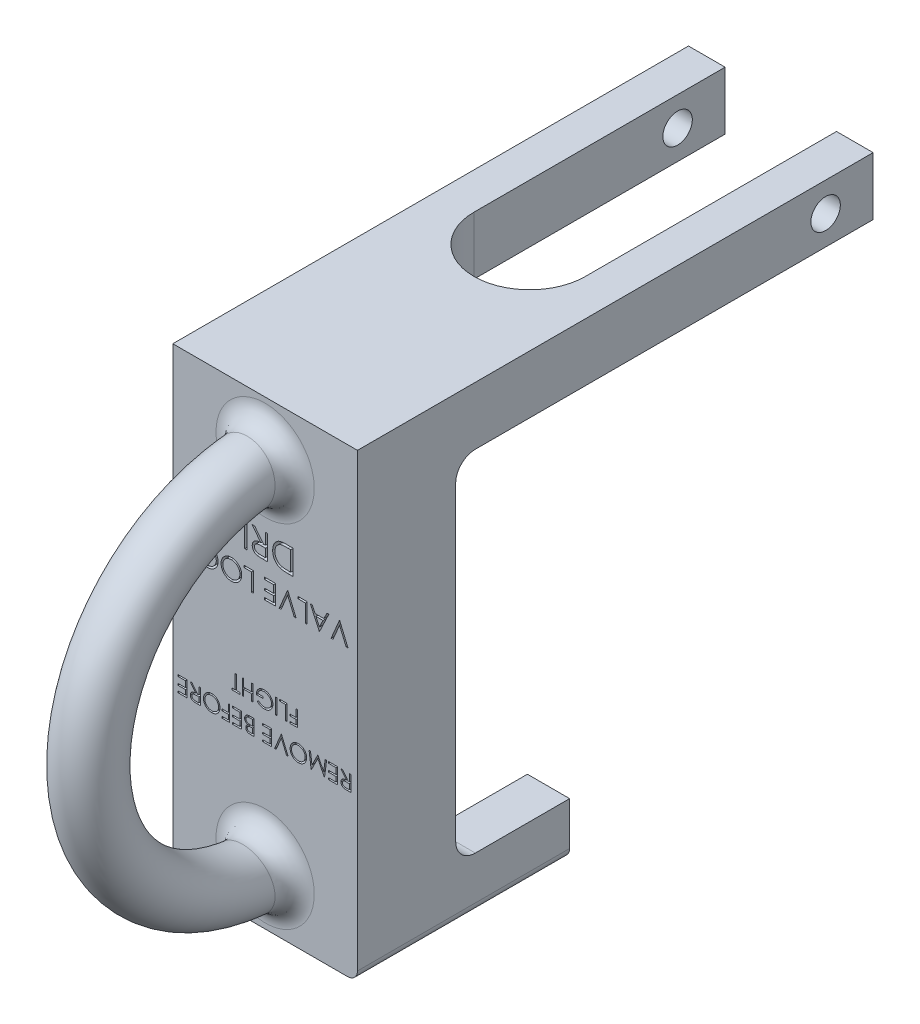
SolidWorks part; units mm, degrees
material "ABS PC"
ref_plane "Front Plane" through (0, 0, 0) normal (0, 0, 1) x (1, 0, 0)
ref_plane "Top Plane" through (0, 0, 0) normal (0, 1, 0) x (1, 0, 0)
ref_plane "Right Plane" through (0, 0, 0) normal (1, 0, 0) x (0, 0, -1)
sketch "Sketch1" plane through (0, 0, 0) normal (0, 0, 1) x (1, 0, 0)
  line L0 (0, 2.5) -> (0, -5) construction
  line L1 (-11.938, -5) -> (11.938, -5)
  line L2 (-11.938, -5) -> (-11.938, 2.5)
  line L3 (-11.938, 2.5) -> (11.938, 2.5)
  line L4 (11.938, -5) -> (11.938, 2.5)
  circle A0 centre (0, 0) radius 1.5
  dimension "D1" = 3
  dimension "D2" = 23.876
  dimension "D3" = 5
  dimension "D4" = 2.5
extrude "Boss-Extrude2" add sketch "Sketch1" along normal blind 21.59 contours L0 L3 L2 L1 A0 | L0 A0 | A0 L0 | L3 L0 A0 L1 L4 region at (6.1881, -1.3014, 0) region at (-6.1881, -1.3014, 0) region at (0.6366, 0, 0) region at (-0.6366, 0, 0)
ref_plane "Plane1" through (0, -1.25, 0) normal (0, 1, 0) x (1, 0, 0)
sketch "Sketch15" plane through (0, 2.5, 0) normal (0, 1, 0) x (1, 0, 0)
  line L0 (-11.938, 0) -> (11.938, 0) construction
  line L1 (-11.938, 0) -> (11.938, 0)
  line L3 (-11.938, 0) -> (11.938, 0)
  line L7 (-7.2, 12.61) -> (7.2, 12.61) construction
  line L10 (-11.938, 0) -> (-11.938, 45.085)
  line L11 (-11.938, 45.085) -> (-7.2, 45.085)
  line L12 (-7.2, 12.61) -> (-7.2, 45.085)
  line L14 (7.2, 12.61) -> (7.2, 45.085)
  line L15 (7.2, 45.085) -> (11.938, 45.085)
  line L16 (11.938, 0) -> (11.938, 45.085)
  arc A0 (-7.2, 12.61) -> (7.2, 12.61) centre (0, 12.61) ccw
  line M5 (11.938, 0) -> (-11.938, 0)
  dimension "D2" = 7.2
  dimension "D1" = 45.085
  dimension "D3" = 12.61
extrude "Boss-Extrude3" add sketch "Sketch15" against normal up to surface (7.5 mm away) contours A0 M5 region at (-11.4278, 2.5, -22.5425) up to face at (0, -5, 10.795)
sketch "Sketch19" plane through (0, -5, 0) normal (0, 1, 0) x (1, 0, 0)
  line L0 (-6.477, -13.462) -> (6.477, -13.462)
  line L1 (-11.938, -21.59) -> (11.938, -21.59) construction
  line L2 (-6.477, -13.462) -> (-6.477, -8.89)
  line L3 (-6.477, -8.89) -> (-11.938, -8.89)
  line L4 (-11.938, -21.59) -> (-11.938, 45.085) construction
  line L5 (-11.938, -8.89) -> (-11.938, -21.59)
  line L6 (-11.938, -21.59) -> (11.938, -21.59)
  line L7 (11.938, -21.59) -> (11.938, -8.89)
  line L8 (11.938, -21.59) -> (11.938, 45.085) construction
  line L9 (11.938, -8.89) -> (6.477, -8.89)
  line L10 (6.477, -8.89) -> (6.477, -13.462)
  point P10 (0, -13.462)
  point P17 (0, -21.59)
  dimension "D1" = 8.128
  dimension "D2" = 12.954
  dimension "D3" = 12.7
extrude "Boss-Extrude4" add sketch "Sketch19" against normal blind 48.26
sketch "Sketch20" plane through (11.938, 0, 0) normal (1, 0, 0) x (0, 0, -1)
  line L0 (45.085, -5) -> (45.085, 2.5) construction
  circle A0 centre (38.9382, -1.25) radius 1.905
  point P5 (45.085, -1.25)
  dimension "D2" = 3.81
  dimension "D1" = 6.1468
extrude "Cut-Extrude1" cut sketch "Sketch20" against normal through all
fillet "Fillet1" radius 2.54 2 edges at (6.477, -29.13, 13.462) (-6.477, -29.13, 13.462)
fillet "Fillet2" radius 2.54 2 edges at (-9.2075, -5, 8.89) (9.2075, -5, 8.89)
fillet "Fillet3" radius 2.54 5 edges at (6.477, -5, 8.636) (5.7331, -5, 12.7181) (0, -5, 13.462) (-5.7331, -5, 12.7181) (-6.477, -5, 8.636)
sketch "Sketch21" plane through (0, 0, 8.89) normal (0, 0, -1) x (-1, 0, 0)
  line L0 (11.938, -53.26) -> (11.938, -7.54) construction
  line L1 (6.477, -53.26) -> (11.938, -53.26)
  line L2 (6.477, -53.26) -> (6.477, -50.212)
  line L3 (6.477, -50.212) -> (11.938, -50.212)
  line L4 (11.938, -53.26) -> (11.938, -50.212)
  line L5 (-11.938, -53.26) -> (-11.938, -7.54) construction
  line L6 (-6.477, -53.26) -> (-11.938, -53.26)
  line L7 (-6.477, -53.26) -> (-6.477, -50.212)
  line L8 (-6.477, -50.212) -> (-11.938, -50.212)
  line L9 (-11.938, -53.26) -> (-11.938, -50.212)
  dimension "D1" = 3.048
extrude "Boss-Extrude5" add sketch "Sketch21" along normal blind 14.732
fillet "Fillet4" radius 2.54 2 edges at (-9.2075, -50.212, 8.89) (9.2075, -50.212, 8.89)
sketch "Sketch29" plane through (0, 0, 21.59) normal (0, 0, 1) x (1, 0, 0)
  line L0 (11.938, -34.21) -> (-11.938, -34.21) construction
  line L1 (11.938, -53.26) -> (11.938, 2.5) construction
  line L2 (-11.938, -53.26) -> (-11.938, 2.5) construction
  line L3 (11.938, -17.7) -> (-11.938, -17.7) construction
  line L4 (11.938, -30.4) -> (-11.938, -30.4) construction
  line L5 (11.938, -12.62) -> (-11.938, -12.62) construction
  line L6 (-11.938, -53.26) -> (11.938, -53.26) construction
  text T0 "REMOVE BEFORE" font "Century Gothic" height 2.032
  text T1 "FLIGHT" font "Century Gothic" height 2.032
  text T2 "VALVE LOCK" font "Century Gothic" height 2.54
  text T3 "DRL"
  dimension "D1" = 3.81
  dimension "D2" = 19.05
  dimension "D3" = 12.7
  dimension "D4" = 5.08
extrude "Cut-Extrude2" cut sketch "Sketch29" against normal blind 2.54
sketch "Sketch30" plane through (0, -53.26, 0) normal (0, -1, 0) x (1, 0, 0)
  line L14 (-6.477, -5.842) -> (-6.477, 10.922)
  line L15 (-3.937, 13.462) -> (3.937, 13.462)
  line L24 (6.477, 10.922) -> (6.477, -5.842)
  line L25 (6.477, -5.842) -> (11.938, -5.842)
  line L26 (11.938, -5.842) -> (11.938, 21.59)
  line L27 (11.938, 21.59) -> (-11.938, 21.59)
  line L28 (-11.938, 21.59) -> (-11.938, -5.842)
  line L29 (-11.938, -5.842) -> (-6.477, -5.842)
  line L30 (-6.477, -5.842) -> (-6.477, 10.922)
  line L31 (-3.937, 13.462) -> (3.937, 13.462)
  line L32 (6.477, 10.922) -> (6.477, -5.842)
  line L33 (6.477, -5.842) -> (11.938, -5.842)
  line L34 (11.938, -5.842) -> (11.938, 21.59)
  line L35 (11.938, 21.59) -> (-11.938, 21.59)
  line L36 (-11.938, 21.59) -> (-11.938, -5.842)
  line L37 (-11.938, -5.842) -> (-6.477, -5.842)
  arc A6 (-3.937, 13.462) -> (-6.477, 10.922) centre (-3.937, 10.922) ccw
  arc A7 (6.477, 10.922) -> (3.937, 13.462) centre (3.937, 10.922) ccw
  arc A8 (-3.937, 13.462) -> (-6.477, 10.922) centre (-3.937, 10.922) ccw
  arc A9 (6.477, 10.922) -> (3.937, 13.462) centre (3.937, 10.922) ccw
  dimension "D1" = 0
extrude "Boss-Extrude6" add sketch "Sketch30" along normal blind 3.81
sketch "Sketch2" plane through (0, -25.38, 0) normal (1, 0, 0) x (0, -1, 0)
  line L1 (31.69, -21.59) -> (-27.88, -21.59) construction
  line L2 (31.69, -21.59) -> (-27.88, -21.59) construction
  arc A0 (-20.955, -21.59) -> (24.765, -21.59) centre (1.905, -21.59) ccw
  dimension "D1" = 22.86
sweep "Sweep1" add path "Sketch2" circular profile diameter 7.62 parameters "D3"=7.62
fillet "Fillet6" radius 2.54 2 edges at (3.81, -50.145, 21.59) (3.81, -4.425, 21.59)
fillet "Fillet9" radius 1.27 2 edges at (-11.938, -57.07, 7.874) (11.938, -57.07, 7.874)
